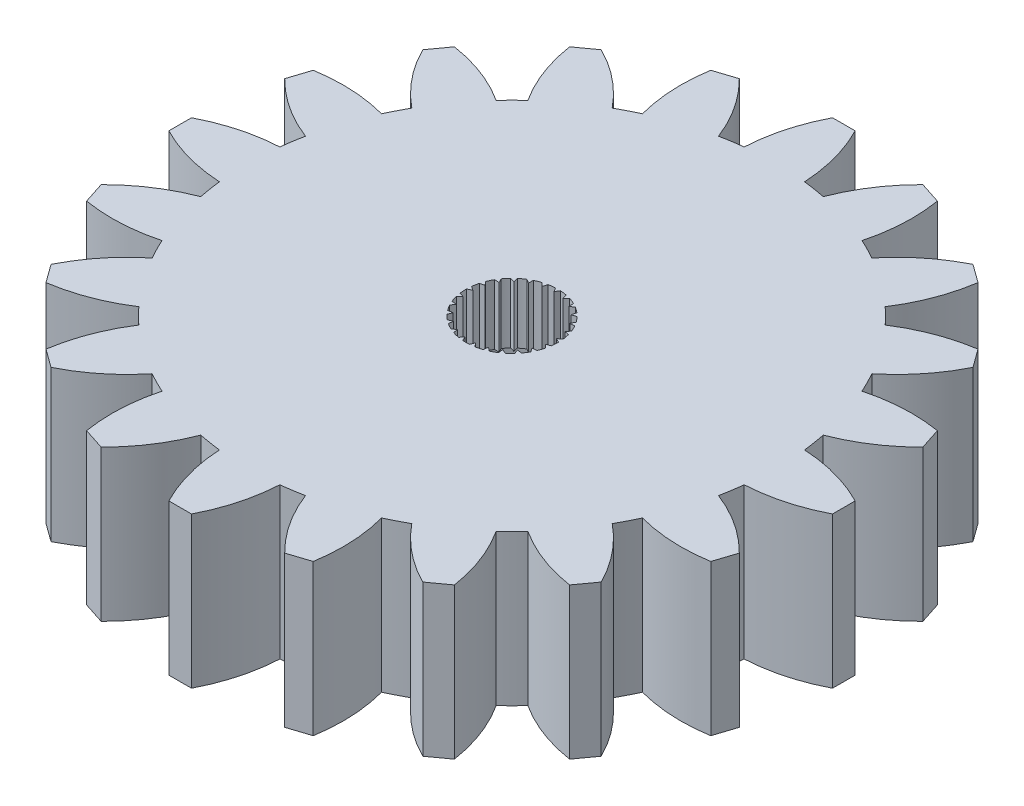
SolidWorks part; units mm, degrees
ref_plane "Front Plane" through (0, 0, 0) normal (0, 0, 1) x (1, 0, 0)
ref_plane "Top Plane" through (0, 0, 0) normal (0, 1, 0) x (1, 0, 0)
ref_plane "Right Plane" through (0, 0, 0) normal (1, 0, 0) x (0, 0, -1)
sketch "Sketch2" plane through (0, 0, 0) normal (0, 1, 0) x (1, 0, 0)
  line L0 (0, -10.2886) -> (0, 10.2886) construction
  line L1 (0, 0) -> (0.6267, 4.1579) construction
  line L2 (0, 0) -> (-0.6267, 4.1579) construction
  line L3 (0, 0) -> (1.373, 17.4461) construction
  line L4 (0, 0) -> (-1.373, 17.4461) construction
  line L5 (-0.1565, 3.046) -> (0, 2.775)
  line L6 (0, 2.775) -> (0.1565, 3.046)
  line L7 (-0.75, 21.9872) -> (0.75, 21.9872)
  line L8 (0.6901, 2.6878) -> (0.909, 2.9114)
  line L9 (7.8676, 46.3212) -> (7.9539, 46.8293)
  line L10 (3.8992, 46.8226) -> (3.9419, 47.3362)
  line L11 (0.606, 2.9892) -> (0.6901, 2.6878)
  line L12 (13.6112, 44.9699) -> (13.7605, 45.4632)
  line L13 (9.7368, 45.9647) -> (9.8436, 46.4688)
  line L14 (1.3369, 2.4318) -> (1.6045, 2.5938)
  line L15 (19.1401, 42.9094) -> (19.35, 43.38)
  line L16 (15.421, 44.3819) -> (15.5901, 44.8687)
  line L17 (1.3303, 2.7446) -> (1.3369, 2.4318)
  line L18 (24.3671, 40.1721) -> (24.6344, 40.6128)
  line L19 (20.8619, 42.0991) -> (21.0907, 42.5609)
  line L20 (1.8996, 2.0229) -> (2.1992, 2.1133)
  line L21 (29.2099, 36.8013) -> (29.5303, 37.205)
  line L22 (25.9738, 39.1525) -> (26.2587, 39.5819)
  line L23 (1.9711, 2.3275) -> (1.8996, 2.0229)
  line L24 (33.592, 32.8502) -> (33.9604, 33.2105)
  line L25 (30.6761, 35.5884) -> (31.0126, 35.9787)
  line L26 (2.343, 1.4869) -> (2.6556, 1.5)
  line L27 (37.4443, 28.381) -> (37.855, 28.6923)
  line L28 (34.8946, 31.463) -> (35.2774, 31.8081)
  line L29 (2.488, 1.7642) -> (2.343, 1.4869)
  line L30 (40.7061, 23.4641) -> (41.1526, 23.7215)
  line L31 (38.5628, 26.8415) -> (38.9858, 27.1359)
  line L32 (2.6392, 0.8575) -> (2.9453, 0.7925)
  line L33 (43.326, 18.1773) -> (43.8012, 18.3767)
  line L34 (41.6229, 21.7966) -> (42.0794, 22.0357)
  line L35 (2.8486, 1.0901) -> (2.6392, 0.8575)
  line L36 (45.2626, 12.6038) -> (45.7591, 12.742)
  line L37 (44.0265, 16.408) -> (44.5094, 16.588)
  line L38 (2.7695, 0.1742) -> (3.0498, 0.0351)
  line L39 (46.4853, 6.8315) -> (46.9952, 6.9064)
  line L40 (45.7358, 10.7606) -> (46.2375, 10.8787)
  line L41 (3.0302, 0.3474) -> (2.7695, 0.1742)
  line L42 (46.975, 0.9515) -> (47.4903, 0.9619)
  line L43 (46.7238, 4.9436) -> (47.2363, 4.9978)
  line L44 (2.7258, -0.52) -> (2.9627, -0.7244)
  line L45 (46.7238, -4.9436) -> (47.2363, -4.9978)
  line L46 (46.975, -0.9515) -> (47.4903, -0.9619)
  line L47 (3.0213, -0.4171) -> (2.7258, -0.52)
  line L48 (45.7358, -10.7606) -> (46.2375, -10.8787)
  line L49 (46.4853, -6.8315) -> (46.9952, -6.9064)
  line L50 (2.5109, -1.1815) -> (2.6895, -1.4385)
  line L51 (44.0265, -16.408) -> (44.5094, -16.588)
  line L52 (45.2626, -12.6038) -> (45.7591, -12.742)
  line L53 (2.8227, -1.1554) -> (2.5109, -1.1815)
  line L54 (41.6229, -21.7966) -> (42.0794, -22.0357)
  line L55 (43.326, -18.1773) -> (43.8012, -18.3767)
  line L56 (2.1382, -1.7689) -> (2.2472, -2.0621)
  line L57 (38.5628, -26.8415) -> (38.9858, -27.1359)
  line L58 (40.7061, -23.4641) -> (41.1526, -23.7215)
  line L59 (2.4467, -1.821) -> (2.1382, -1.7689)
  line L60 (34.8946, -31.463) -> (35.2774, -31.8081)
  line L61 (37.4443, -28.381) -> (37.855, -28.6923)
  line L62 (1.6311, -2.245) -> (1.6638, -2.5562)
  line L63 (30.6761, -35.5884) -> (31.0126, -35.9787)
  line L64 (33.592, -32.8502) -> (33.9604, -33.2105)
  line L65 (1.917, -2.3723) -> (1.6311, -2.245)
  line L66 (25.9738, -39.1525) -> (26.2587, -39.5819)
  line L67 (29.2099, -36.8013) -> (29.5303, -37.205)
  line L68 (1.0215, -2.5801) -> (0.9758, -2.8897)
  line L69 (20.8619, -42.0991) -> (21.0907, -42.5609)
  line L70 (24.3671, -40.1721) -> (24.6344, -40.6128)
  line L71 (1.2668, -2.7745) -> (1.0215, -2.5801)
  line L72 (15.421, -44.3819) -> (15.5901, -44.8687)
  line L73 (19.1401, -42.9094) -> (19.35, -43.38)
  line L74 (0.3478, -2.7531) -> (0.2265, -3.0416)
  line L75 (9.7368, -45.9647) -> (9.8436, -46.4688)
  line L76 (13.6112, -44.9699) -> (13.7605, -45.4632)
  line L77 (0.537, -3.0024) -> (0.3478, -2.7531)
  line L78 (3.8992, -46.8226) -> (3.9419, -47.3362)
  line L79 (7.8676, -46.3212) -> (7.9539, -46.8293)
  line L80 (-0.3478, -2.7531) -> (-0.537, -3.0024)
  line L81 (-2, -46.942) -> (-2.0219, -47.4569)
  line L82 (2, -46.942) -> (2.0219, -47.4569)
  line L83 (-0.2265, -3.0416) -> (-0.3478, -2.7531)
  line L84 (-7.8676, -46.3212) -> (-7.9539, -46.8293)
  line L85 (-3.8992, -46.8226) -> (-3.9419, -47.3362)
  line L86 (-1.0215, -2.5801) -> (-1.2668, -2.7745)
  line L87 (-13.6112, -44.9699) -> (-13.7605, -45.4632)
  line L88 (-9.7368, -45.9647) -> (-9.8436, -46.4688)
  line L89 (-0.9758, -2.8897) -> (-1.0215, -2.5801)
  line L90 (-19.1401, -42.9094) -> (-19.35, -43.38)
  line L91 (-15.421, -44.3819) -> (-15.5901, -44.8687)
  line L92 (-1.6311, -2.245) -> (-1.917, -2.3723)
  line L93 (-24.3671, -40.1721) -> (-24.6344, -40.6128)
  line L94 (-20.8619, -42.0991) -> (-21.0907, -42.5609)
  line L95 (-1.6638, -2.5562) -> (-1.6311, -2.245)
  line L96 (-29.2099, -36.8013) -> (-29.5303, -37.205)
  line L97 (-25.9738, -39.1525) -> (-26.2587, -39.5819)
  line L98 (-2.1382, -1.7689) -> (-2.4467, -1.821)
  line L99 (-33.592, -32.8502) -> (-33.9604, -33.2105)
  line L100 (-30.6761, -35.5884) -> (-31.0126, -35.9787)
  line L101 (-2.2472, -2.0621) -> (-2.1382, -1.7689)
  line L102 (-37.4443, -28.381) -> (-37.855, -28.6923)
  line L103 (-34.8946, -31.463) -> (-35.2774, -31.8081)
  line L104 (-2.5109, -1.1815) -> (-2.8227, -1.1554)
  line L105 (-40.7061, -23.4641) -> (-41.1526, -23.7215)
  line L106 (-38.5628, -26.8415) -> (-38.9858, -27.1359)
  line L107 (-2.6895, -1.4385) -> (-2.5109, -1.1815)
  line L108 (-43.326, -18.1773) -> (-43.8012, -18.3767)
  line L109 (-41.6229, -21.7966) -> (-42.0794, -22.0357)
  line L110 (-2.7258, -0.52) -> (-3.0213, -0.4171)
  line L111 (-45.2626, -12.6038) -> (-45.7591, -12.742)
  line L112 (-44.0265, -16.408) -> (-44.5094, -16.588)
  line L113 (-2.9627, -0.7244) -> (-2.7258, -0.52)
  line L114 (-46.4853, -6.8315) -> (-46.9952, -6.9064)
  line L115 (-45.7358, -10.7606) -> (-46.2375, -10.8787)
  line L116 (-2.7695, 0.1742) -> (-3.0302, 0.3474)
  line L117 (-46.975, -0.9515) -> (-47.4903, -0.9619)
  line L118 (-46.7238, -4.9436) -> (-47.2363, -4.9978)
  line L119 (-3.0498, 0.0351) -> (-2.7695, 0.1742)
  line L120 (-46.7238, 4.9436) -> (-47.2363, 4.9978)
  line L121 (-46.975, 0.9515) -> (-47.4903, 0.9619)
  line L122 (-2.6392, 0.8575) -> (-2.8486, 1.0901)
  line L123 (-45.7358, 10.7606) -> (-46.2375, 10.8787)
  line L124 (-46.4853, 6.8315) -> (-46.9952, 6.9064)
  line L125 (-2.9453, 0.7925) -> (-2.6392, 0.8575)
  line L126 (-44.0265, 16.408) -> (-44.5094, 16.588)
  line L127 (-45.2626, 12.6038) -> (-45.7591, 12.742)
  line L128 (-2.343, 1.4869) -> (-2.488, 1.7642)
  line L129 (-41.6229, 21.7966) -> (-42.0794, 22.0357)
  line L130 (-43.326, 18.1773) -> (-43.8012, 18.3767)
  line L131 (-2.6556, 1.5) -> (-2.343, 1.4869)
  line L132 (-38.5628, 26.8415) -> (-38.9858, 27.1359)
  line L133 (-40.7061, 23.4641) -> (-41.1526, 23.7215)
  line L134 (-1.8996, 2.0229) -> (-1.9711, 2.3275)
  line L135 (-34.8946, 31.463) -> (-35.2774, 31.8081)
  line L136 (-37.4443, 28.381) -> (-37.855, 28.6923)
  line L137 (-2.1992, 2.1133) -> (-1.8996, 2.0229)
  line L138 (-30.6761, 35.5884) -> (-31.0126, 35.9787)
  line L139 (-33.592, 32.8502) -> (-33.9604, 33.2105)
  line L140 (-1.3369, 2.4318) -> (-1.3303, 2.7446)
  line L141 (-25.9738, 39.1525) -> (-26.2587, 39.5819)
  line L142 (-29.2099, 36.8013) -> (-29.5303, 37.205)
  line L143 (-1.6045, 2.5938) -> (-1.3369, 2.4318)
  line L144 (-20.8619, 42.0991) -> (-21.0907, 42.5609)
  line L145 (-24.3671, 40.1721) -> (-24.6344, 40.6128)
  line L146 (-0.6901, 2.6878) -> (-0.606, 2.9892)
  line L147 (-15.421, 44.3819) -> (-15.5901, 44.8687)
  line L148 (-19.1401, 42.9094) -> (-19.35, 43.38)
  line L149 (-0.909, 2.9114) -> (-0.6901, 2.6878)
  line L150 (-9.7368, 45.9647) -> (-9.8436, 46.4688)
  line L151 (-13.6112, 44.9699) -> (-13.7605, 45.4632)
  line L153 (-3.8992, 46.8226) -> (-3.9419, 47.3362)
  line L154 (-7.8676, 46.3212) -> (-7.9539, 46.8293)
  circle A0 centre (0, 0) radius 18.7939 construction
  circle A1 centre (0, 0) radius 2.775 construction
  circle A2 centre (0, 0) radius 3.05
  circle A24 centre (0, 0) radius 17.5
  circle A25 centre (0, 0) radius 20 construction
  circle A26 centre (0, 0) radius 22 construction
  arc A27 (0.75, 21.9872) -> (2, 17.3853) centre (-9.2545, 16.799) cw
  arc A28 (-0.75, 21.9872) -> (-2, 17.3853) centre (9.2545, 16.799) ccw
  point P7 (0, 0)
  point P12 (0, 0)
  point P26 (0, 0)
  point P28 (0, 0)
  point P30 (1.5692, 19.9383)
  point P78 (0, 0)
  point P139 (0, 0)
  point P226 (0, 0)
  dimension "D1" = 5.55
  dimension "D3" = 6.1
  dimension "D5" = 37.5877
  dimension "D6" = 35
  dimension "D7" = 40
  dimension "D8" = 44
  dimension "D2" = 8.571
  dimension "D9" = 4.5
  dimension "D11" = 1.5
  dimension "D12" = 4
  dimension "D4" = 60
  dimension "D10" = 30
  dimension "D13" = 25
extrude "Boss-Extrude1" add sketch "Sketch2" along normal blind 10 contours A24 | A2 region at (0, 0, -17.005)
extrude "Boss-Extrude2" add sketch "Sketch2<4>" along normal up to surface (10 mm away) contours L7 A28 A24 A27 region at (0, 0, -19.4231) up to face at (0, 10, 17.5)
sketch "Sketch2<4>" plane through (0, 0, 0) normal (0, 1, 0) x (1, 0, 0) same geometry as "Sketch2"
pattern_circular "CirPattern1" count 20 over 360 about axis through (0, 10, 0) along (0, 1, 0) of "Boss-Extrude2"
extrude "Cut-Extrude2" cut sketch "Sketch2<7>" against normal blind 4 from surface contours L77 A2 L68 L71 L62 L65 L56 L59 L50 L53 L44 L47 L38 L41 L32 L35 L26 L29 L20 L23 L14 L17 L8 L11 L6 L5 L146 L149 L140 L143 L134 L137 L128 L131 L122 region at (0, 0, 0) starting at face at (0, 10, 0)
sketch "Sketch2<7>" plane through (0, 0, 0) normal (0, 1, 0) x (1, 0, 0) same geometry as "Sketch2"
sketch "Sketch3" plane through (0, 0, 0) normal (0, -1, 0) x (1, 0, 0)
  circle A0 centre (0, 0) radius 5
  dimension "D1" = 10
extrude "Cut-Extrude3" cut sketch "Sketch3" against normal up to surface (6 mm away) up to face at (0, 6, 0)
equation "\"Module\"= 2"
equation "\"Teeth\"= 20"
equation "\"Pitch Diameter\"= \"Module\" * \"Teeth\""
equation "\"Outer Diamter\"= \"Pitch Diameter\" + ( 2 * \"Module\" )"
equation "\"Root Diameter\"= \"Pitch Diameter\" - ( 2.5 * \"Module\" )"
equation "\"Base Diamter\"= \"Pitch Diameter\" * cos ( 20 )"
equation "\"D5@Sketch2\"=\"Base Diamter\""
equation "\"D6@Sketch2\"=\"Root Diameter\""
equation "\"D8@Sketch2\"=\"Outer Diamter\""
equation "\"D9@Sketch2\"=90 / \"Teeth\""
equation "\"D7@Sketch2\"=\"Pitch Diameter\""
equation "\"D1@CirPattern1\"=\"Teeth\""
